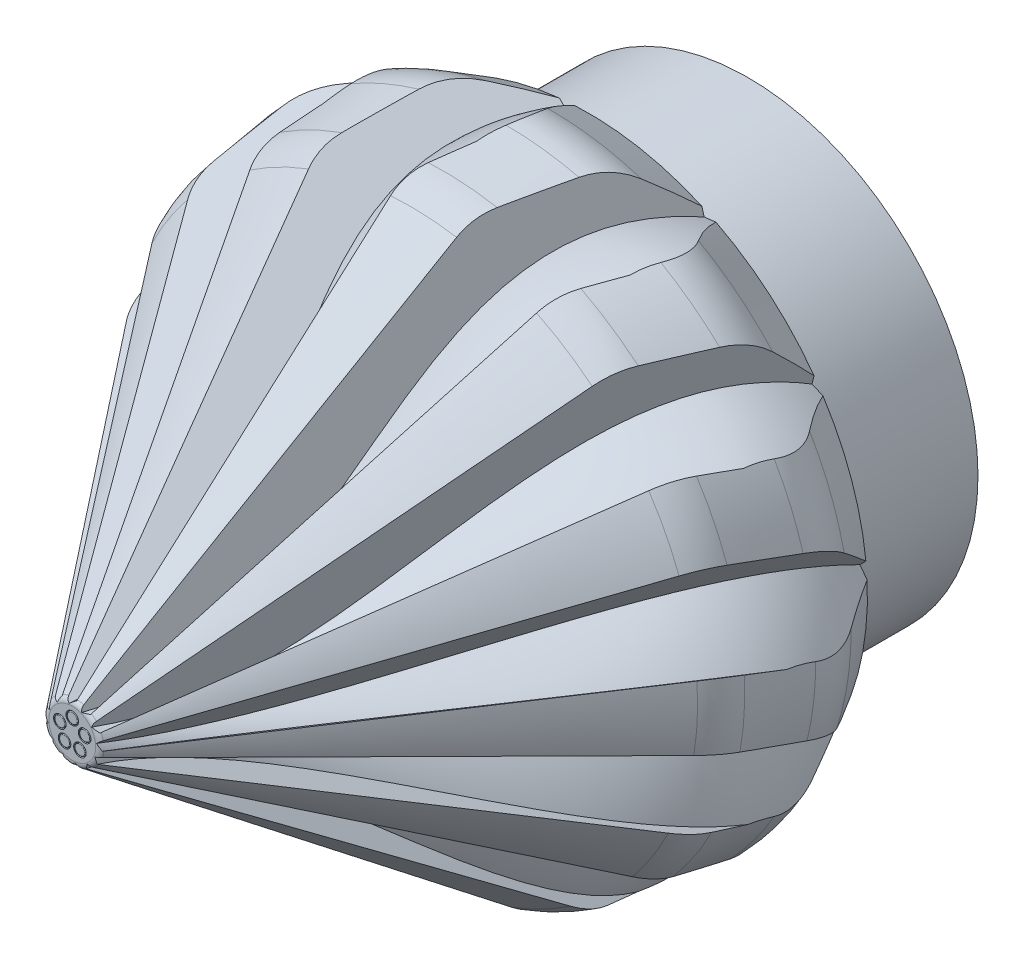
SolidWorks part; units mm, degrees
note: The reader was unsure of these and kept them because the rebuilt part matched: shared geometry of "草图7<2>".
ref_plane "前视基准面" through (0, 0, 0) normal (0, 0, 1) x (1, 0, 0)
ref_plane "上视基准面" through (0, 0, 0) normal (0, 1, 0) x (1, 0, 0)
ref_plane "右视基准面" through (0, 0, 0) normal (1, 0, 0) x (0, 0, -1)
other "Configuration Table"
sketch "草图1" plane through (0, 0, 0) normal (1, 0, 0) x (0, 0, -1)
  line L0 (0, 0) -> (-100, 0) construction
  line L1 (0, 0) -> (0, 34) construction
  line L2 (0, 34) -> (-10.4754, 34)
  line L3 (-10.4754, 34) -> (-36.4562, 49)
  line L4 (-36.4562, 49) -> (-100, 0)
  line L5 (0, 34) -> (2, 34)
  line L6 (2, 34) -> (2, 0)
  line L7 (2, 0) -> (-100, 0)
revolve "旋转2" add sketch "草图1" angle 360 about L7
chamfer "倒角1" distance 10 angle 30 1 edges at (0, 49, 36.4562)
sketch "草图2" plane through (0, 0, 0) normal (0, 1, 0) x (1, 0, 0)
  line L0 (0, -100) -> (0, -95)
  line L1 (0, -95) -> (6.4841, -95)
  line L2 (6.4841, -95) -> (5.5584, -105.4661)
  line L3 (5.5584, -105.4661) -> (-10.5199, -103.137)
  line L4 (-10.5199, -103.137) -> (-9.3411, -95)
  line L5 (-9.3411, -95) -> (0, -95)
extrude "切除-拉伸1" cut sketch "草图2" against normal through all both and the other way through all
fillet "圆角2" radius 10 2 edges at (0, -42.8935, 44.3752) (0, 44.906, 29.3652)
fillet "圆角3" radius 1 1 edges at (3.8556, 0, 95)
sketch "草图4" plane through (0, 0, 0) normal (1, 0, 0) x (0, 0, -1)
  line L0 (-10.4754, 34) -> (-26.4139, 43.2021) construction
  line L1 (-95, 3.3639) -> (-102.2736, 3.3639)
  line L2 (-102.2736, 3.3639) -> (-102.2736, 58.6135)
  line L3 (-102.2736, 58.6135) -> (-12.289, 58.6135)
  line L4 (-12.289, 58.6135) -> (-14.4451, 36.2919)
  line L5 (0, 0) -> (-142.3251, 0.6636) construction
  spline S0 degree 3 poles (-95, 3.3639) (-61.09, 1.9856) (-50.605, 49.1531) (-14.4451, 36.2919) knots 0 0 0 0 1 1 1 1
sketch "草图5" plane through (0, 0, 0) normal (0, 1, 0) x (1, 0, 0)
  line L0 (0, -101.8532) -> (13.7793, -59.8176)
  line L1 (0, 0) -> (0, -142.3251) construction
ref_plane "基准面1" through (30.148, 0, 9.8825) normal (0.9502, 0, 0.3115) x (0.3115, 0, -0.9502)
sketch "草图6" plane through (30.148, 0, 9.8825) normal (0.9502, 0, 0.3115) x (0.3115, 0, -0.9502)
  line L0 (-11.6776, 58.6135) -> (-13.7264, 36.2919) construction
  line L1 (-97.1854, 3.3639) -> (-97.1854, 58.6135) construction
  line L2 (-97.1854, 58.6135) -> (-11.6776, 58.6135) construction
  line L3 (-11.6776, 58.6135) -> (-13.7264, 36.2919)
  line L4 (-97.1854, 3.3639) -> (-97.1854, 58.6135)
  line L5 (-97.1854, 58.6135) -> (-11.6776, 58.6135)
  line L7 (0, 0) -> (-117.3759, 0) construction
  line L8 (-90.2736, 3.3639) -> (-97.1854, 3.3639)
  spline S0 degree 3 poles (-1062.6446, 1748.2712) (712.104, -1927.0592) (-809.2693, 1980.2133) (907.9956, -1736.8546) knots -2.14237 -2.14237 -2.14237 -2.14237 3.050863 3.050863 3.050863 3.050863 only from (-90.2736, 3.3639) to (-13.7264, 36.2919) construction
  spline S1 degree 3 poles (-90.2736, 3.3639) (-58.0507, 1.9856) (-48.0873, 49.1531) (-13.7264, 36.2919) knots 0 0 0 0 1 1 1 1
revolve "切除-旋转2" cut sketch "草图6" angle 15 about L7
pattern_circular "阵列(圆周)1" count 12 every 30 of "切除-旋转2"
sketch "草图7" plane through (0, 0, -2) normal (0, 0, -1) x (-1, 0, 0)
  circle A0 centre (0, 0) radius 1.5
extrude "切除-拉伸2" cut sketch "草图7" against normal blind 2
sketch "草图8" plane through (0, 0, 0) normal (1, 0, 0) x (0, 0, -1)
  line L0 (2, 0) -> (2, 40)
  line L1 (2, -34) -> (2, 34) construction
  line L2 (2, 40) -> (-20.8677, 40)
  line L3 (-10.4754, 34) -> (-26.4139, 43.2021) construction
  line L4 (0, 0) -> (36.463, 0) construction
  line L6 (-20.8677, 34) -> (-20.8677, 40)
  line L7 (-20.8677, 34) -> (-20.8677, 33)
  line L8 (-20.8677, 33) -> (2, 33)
revolve "切除-旋转3" cut sketch "草图8" angle 360 about L4
extrude "切除-拉伸3" cut sketch "草图7<2>" against normal blind 10
sketch "草图7<2>" plane through (0, 0, -2) normal (0, 0, -1) x (-1, 0, 0) same geometry as "草图7"
sketch "草图9" plane through (0, 0, 95) normal (0, 0, 1) x (1, 0, 0)
  circle A0 centre (0, 1.8737) radius 0.8
  circle A1 centre (1.782, 0.579) radius 0.8
  circle A2 centre (1.1014, -1.5159) radius 0.8
  circle A3 centre (-1.1014, -1.5159) radius 0.8
  circle A4 centre (-1.782, 0.579) radius 0.8
  point P12 (0, 0)
  dimension "D1" = 5
extrude "切除-拉伸-薄壁1" cut sketch "草图9" against normal blind 10 thin
fillet "圆角4" radius 0.1 5 edges at (-0.982, 0.579, 95) (-0.3014, -1.5159, 95) (1.9014, -1.5159, 95) (2.582, 0.579, 95) (0.8, 1.8737, 95)
